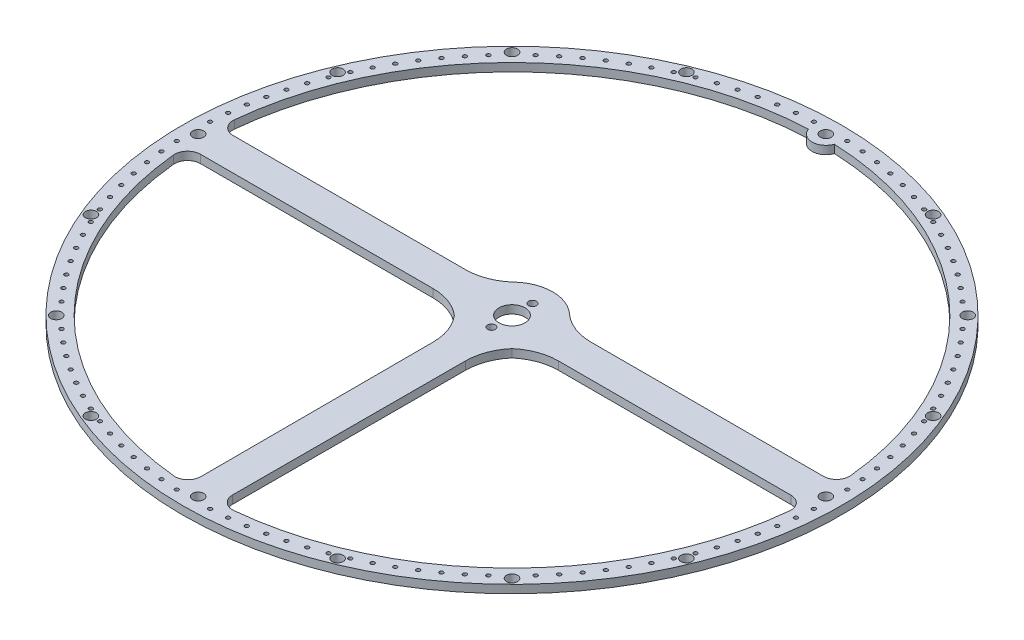
SolidWorks part; units mm, degrees
ref_plane "Front Plane" through (0, 0, 0) normal (0, 0, 1) x (1, 0, 0)
ref_plane "Top Plane" through (0, 0, 0) normal (0, 1, 0) x (1, 0, 0)
ref_plane "Right Plane" through (0, 0, 0) normal (1, 0, 0) x (0, 0, -1)
sketch "Sketch1" plane through (0, 0, 0) normal (0, 1, 0) x (1, 0, 0)
  line L0 (-14.5497, 6.35) -> (-120.6405, 6.35)
  line L1 (120.6405, -6.35) -> (14.5497, -6.35)
  line L3 (120.6405, 6.35) -> (14.5497, 6.35)
  line L12 (6.35, -14.5497) -> (6.171, -120.6498)
  line L13 (-6.35, -14.5497) -> (-6.171, -120.6498)
  line L14 (-14.5497, -6.35) -> (-120.6405, -6.35)
  line L18 (-5.08, 120.7006) -> (-5.08, 110.4973)
  line L19 (-5.08, 110.4973) -> (5.08, 110.4973)
  line L20 (5.08, 120.7006) -> (5.08, 110.4973)
  arc A2 (14.5497, 6.35) -> (-14.5497, 6.35) centre (0, 0) ccw
  arc A3 (-14.5497, -6.35) -> (-6.35, -14.5497) centre (0, 0) ccw
  arc A4 (6.35, -14.5497) -> (14.5497, -6.35) centre (0, 0) ccw
  arc A5 (-120.6405, -6.35) -> (-6.171, -120.6498) centre (0, 0) ccw
  arc A6 (6.171, -120.6498) -> (120.6405, -6.35) centre (0, 0) ccw
  arc A7 (120.6405, 6.35) -> (5.08, 120.7006) centre (0, 0) ccw
  arc A8 (-5.08, 120.7006) -> (-120.6405, 6.35) centre (0, 0) ccw
  point P0 (0, 0)
  dimension "D5" = 31.75
sketch "Screw holes" plane through (0, 0, 0) normal (0, 1, 0) x (1, 0, 0)
  circle A0 centre (0, 8) radius 1.5133
  circle A1 centre (0, -8) radius 1.5133
  circle A2 centre (0, 0) radius 5.08
  dimension "D1" = 16
  dimension "D3" = 3.0266
  dimension "D4" = 10.16
  dimension "D2" = 8
sketch "Sketch4" plane through (0, 0, 0) normal (0, 1, 0) x (1, 0, 0)
  circle A0 centre (0, 0) radius 128.5748
extrude "Boss-Extrude1" add sketch "Sketch4" along normal blind 3.175
extrude "Cut-Extrude2" cut sketch "Sketch1" along normal through all
sketch "Sketch5" plane through (0, 0, 0) normal (0, 1, 0) x (1, 0, 0)
  line L1 (5.08, 120.7006) -> (5.08, 110.4973) construction
  line L2 (5.08, 120.7006) -> (5.08, 110.4973)
  line L3 (5.08, 110.4973) -> (-5.08, 110.4973)
  line L4 (-5.08, 110.4973) -> (-5.08, 120.7006)
  circle A0 centre (0, 122.4534) radius 2.159
  arc A1 (-5.08, 120.7006) -> (5.08, 120.7006) centre (0, 122.4534) ccw
  circle A3 centre (88.9045, -88.9045) radius 2.159
  circle A4 centre (48.1148, -116.1594) radius 2.159
  circle A5 centre (0, -125.73) radius 2.159 [skipped]
  circle A6 centre (-48.1148, -116.1594) radius 2.159
  circle A7 centre (-88.9045, -88.9045) radius 2.159
  circle A8 centre (-116.1594, -48.1148) radius 2.159
  circle A9 centre (-125.73, 0) radius 2.159 [skipped]
  circle A10 centre (-116.1594, 48.1148) radius 2.159
  circle A11 centre (-88.9045, 88.9045) radius 2.159
  circle A12 centre (-48.1148, 116.1594) radius 2.159
  circle A13 centre (0, 125.73) radius 2.159 [skipped]
  circle A14 centre (48.1148, 116.1594) radius 2.159
  circle A15 centre (88.9045, 88.9045) radius 2.159
  circle A16 centre (116.1594, 48.1148) radius 2.159
  circle A17 centre (125.73, 0) radius 2.159 [skipped]
  circle A18 centre (116.1594, -48.1148) radius 2.159
  circle A19 centre (25.8767, -121.7403) radius 0.75
  circle A20 centre (19.4698, -122.9277) radius 0.75
  circle A21 centre (13.0096, -123.7782) radius 0.75
  circle A22 centre (6.5137, -124.2894) radius 0.75
  circle A23 centre (0, -124.46) radius 0.75 [skipped]
  circle A24 centre (-6.5137, -124.2894) radius 0.75
  circle A25 centre (-13.0096, -123.7782) radius 0.75
  circle A26 centre (-19.4698, -122.9277) radius 0.75
  circle A27 centre (-25.8767, -121.7403) radius 0.75
  circle A28 centre (-32.2126, -120.2191) radius 0.75
  circle A29 centre (-38.4603, -118.3685) radius 0.75
  circle A30 centre (-44.6025, -116.1934) radius 0.75
  circle A31 centre (-50.6224, -113.6999) radius 0.75
  circle A32 centre (-56.5037, -110.8947) radius 0.75
  circle A33 centre (-62.23, -107.7855) radius 0.75
  circle A34 centre (-67.7858, -104.3809) radius 0.75
  circle A35 centre (-73.1558, -100.6903) radius 0.75
  circle A36 centre (-78.3252, -96.7236) radius 0.75
  circle A37 centre (-83.28, -92.4918) radius 0.75
  circle A38 centre (-88.0065, -88.0065) radius 0.75 [skipped]
  circle A39 centre (-92.4918, -83.28) radius 0.75
  circle A40 centre (-96.7236, -78.3252) radius 0.75
  circle A41 centre (-100.6903, -73.1558) radius 0.75
  circle A42 centre (-104.3809, -67.7858) radius 0.75
  circle A43 centre (-107.7855, -62.23) radius 0.75
  circle A44 centre (-110.8947, -56.5037) radius 0.75
  circle A45 centre (-113.6999, -50.6224) radius 0.75
  circle A46 centre (-116.1934, -44.6025) radius 0.75
  circle A47 centre (-118.3685, -38.4603) radius 0.75
  circle A48 centre (-120.2191, -32.2126) radius 0.75
  circle A49 centre (-121.7403, -25.8767) radius 0.75
  circle A50 centre (-122.9277, -19.4698) radius 0.75
  circle A51 centre (-123.7782, -13.0096) radius 0.75
  circle A52 centre (-124.2894, -6.5137) radius 0.75
  circle A53 centre (-124.46, 0) radius 0.75 [skipped]
  circle A54 centre (-124.2894, 6.5137) radius 0.75
  circle A55 centre (-123.7782, 13.0096) radius 0.75
  circle A56 centre (-122.9277, 19.4698) radius 0.75
  circle A57 centre (-121.7403, 25.8767) radius 0.75
  circle A58 centre (-120.2191, 32.2126) radius 0.75
  circle A59 centre (-118.3685, 38.4603) radius 0.75
  circle A60 centre (-116.1934, 44.6025) radius 0.75
  circle A61 centre (-113.6999, 50.6224) radius 0.75
  circle A62 centre (-110.8947, 56.5037) radius 0.75
  circle A63 centre (-107.7855, 62.23) radius 0.75
  circle A64 centre (-104.3809, 67.7858) radius 0.75
  circle A65 centre (-100.6903, 73.1558) radius 0.75
  circle A66 centre (-96.7236, 78.3252) radius 0.75
  circle A67 centre (-92.4918, 83.28) radius 0.75
  circle A68 centre (-88.0065, 88.0065) radius 0.75 [skipped]
  circle A69 centre (-83.28, 92.4918) radius 0.75
  circle A70 centre (-78.3252, 96.7236) radius 0.75
  circle A71 centre (-73.1558, 100.6903) radius 0.75
  circle A72 centre (-67.7858, 104.3809) radius 0.75
  circle A73 centre (-62.23, 107.7855) radius 0.75
  circle A74 centre (-56.5037, 110.8947) radius 0.75
  circle A75 centre (-50.6224, 113.6999) radius 0.75
  circle A76 centre (-44.6025, 116.1934) radius 0.75
  circle A77 centre (-38.4603, 118.3685) radius 0.75
  circle A78 centre (-32.2126, 120.2191) radius 0.75
  circle A79 centre (-25.8767, 121.7403) radius 0.75
  circle A80 centre (-19.4698, 122.9277) radius 0.75
  circle A81 centre (-13.0096, 123.7782) radius 0.75
  circle A82 centre (-6.5137, 124.2894) radius 0.75
  circle A83 centre (0, 124.46) radius 0.75 [skipped]
  circle A84 centre (6.5137, 124.2894) radius 0.75
  circle A85 centre (13.0096, 123.7782) radius 0.75
  circle A86 centre (19.4698, 122.9277) radius 0.75
  circle A87 centre (25.8767, 121.7403) radius 0.75
  circle A88 centre (32.2126, 120.2191) radius 0.75
  circle A89 centre (38.4603, 118.3685) radius 0.75
  circle A90 centre (44.6025, 116.1934) radius 0.75
  circle A91 centre (50.6224, 113.6999) radius 0.75
  circle A92 centre (56.5037, 110.8947) radius 0.75
  circle A93 centre (62.23, 107.7855) radius 0.75
  circle A94 centre (67.7858, 104.3809) radius 0.75
  circle A95 centre (73.1558, 100.6903) radius 0.75
  circle A96 centre (78.3252, 96.7236) radius 0.75
  circle A97 centre (83.28, 92.4918) radius 0.75
  circle A98 centre (88.0065, 88.0065) radius 0.75 [skipped]
  circle A99 centre (92.4918, 83.28) radius 0.75
  circle A100 centre (96.7236, 78.3252) radius 0.75
  circle A101 centre (100.6903, 73.1558) radius 0.75
  circle A102 centre (104.3809, 67.7858) radius 0.75
  circle A103 centre (107.7855, 62.23) radius 0.75
  circle A104 centre (110.8947, 56.5037) radius 0.75
  circle A105 centre (113.6999, 50.6224) radius 0.75
  circle A106 centre (116.1934, 44.6025) radius 0.75
  circle A107 centre (118.3685, 38.4603) radius 0.75
  circle A108 centre (120.2191, 32.2126) radius 0.75
  circle A109 centre (121.7403, 25.8767) radius 0.75
  circle A110 centre (122.9277, 19.4698) radius 0.75
  circle A111 centre (123.7782, 13.0096) radius 0.75
  circle A112 centre (124.2894, 6.5137) radius 0.75
  circle A113 centre (124.46, 0) radius 0.75 [skipped]
  circle A114 centre (124.2894, -6.5137) radius 0.75
  circle A115 centre (123.7782, -13.0096) radius 0.75
  circle A116 centre (122.9277, -19.4698) radius 0.75
  circle A117 centre (121.7403, -25.8767) radius 0.75
  circle A118 centre (120.2191, -32.2126) radius 0.75
  circle A119 centre (118.3685, -38.4603) radius 0.75
  circle A120 centre (116.1934, -44.6025) radius 0.75
  circle A121 centre (113.6999, -50.6224) radius 0.75
  circle A122 centre (110.8947, -56.5037) radius 0.75
  circle A123 centre (107.7855, -62.23) radius 0.75
  circle A124 centre (104.3809, -67.7858) radius 0.75
  circle A125 centre (100.6903, -73.1558) radius 0.75
  circle A126 centre (96.7236, -78.3252) radius 0.75
  circle A127 centre (92.4918, -83.28) radius 0.75
  circle A128 centre (88.0065, -88.0065) radius 0.75 [skipped]
  circle A129 centre (83.28, -92.4918) radius 0.75
  circle A130 centre (78.3252, -96.7236) radius 0.75
  circle A131 centre (73.1558, -100.6903) radius 0.75
  circle A132 centre (67.7858, -104.3809) radius 0.75
  circle A133 centre (62.23, -107.7855) radius 0.75
  circle A134 centre (56.5037, -110.8947) radius 0.75
  circle A135 centre (50.6224, -113.6999) radius 0.75
  circle A136 centre (44.6025, -116.1934) radius 0.75
  circle A137 centre (38.4603, -118.3685) radius 0.75
  circle A138 centre (32.2126, -120.2191) radius 0.75
  point P49 (0, 0)
  point P291 (0, 0)
  dimension "D3" = 4.318
  dimension "D7" = 1.5
  dimension "D2" = 122.4534
  dimension "D4" = 16
  dimension "D8" = 120
extrude "Cut-Extrude3" cut sketch "Sketch5" along normal through all
extrude "middle holes" cut sketch "Screw holes" along normal through all
fillet "Filletmiddle" radius 20.32 6 edges at (14.5497, 1.5875, -6.35) (-14.5497, 1.5875, -6.35) (14.5497, 1.5875, 6.35) (6.35, 1.5875, 14.5497) (-14.5497, 1.5875, 6.35) (-6.35, 1.5875, 14.5497)
fillet "Filletsides" radius 5.08 6 edges at (120.6405, 1.5875, 6.35) (120.6405, 1.5875, -6.35) (-6.171, 1.5875, 120.6498) (6.171, 1.5875, 120.6498) (-120.6405, 1.5875, 6.35) (-120.6405, 1.5875, -6.35)
sketch "Sketch6" plane through (0, 0, 0) normal (0, 1, 0) x (1, 0, 0)
  circle A0 centre (-122.4534, 0) radius 2.159
  circle A1 centre (0, -122.4534) radius 2.159
  circle A2 centre (122.4534, 0) radius 2.159
  dimension "D1" = 122.4534
  dimension "D2" = 122.4534
  dimension "D3" = 122.4534
extrude "Cut-Extrude5" cut sketch "Sketch6" along normal through all
